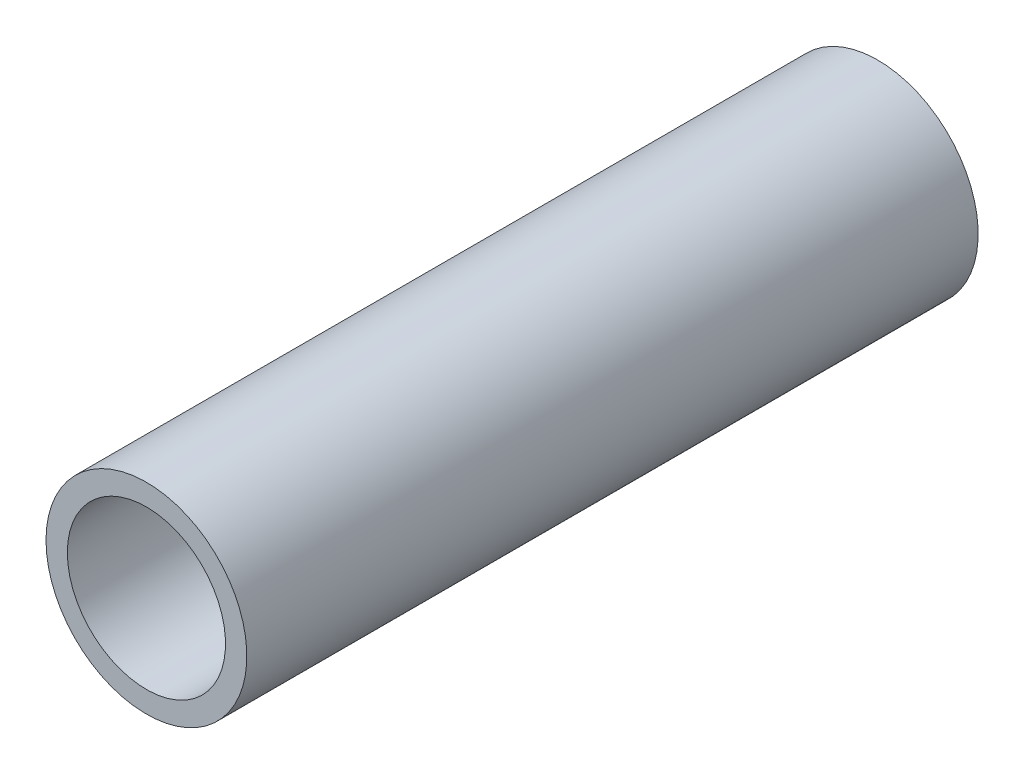
SolidWorks part; units mm, degrees
ref_plane "Front Plane" through (0, 0, 0) normal (0, 0, 1) x (1, 0, 0)
ref_plane "Top Plane" through (0, 0, 0) normal (0, 1, 0) x (1, 0, 0)
ref_plane "Right Plane" through (0, 0, 0) normal (1, 0, 0) x (0, 0, -1)
sketch "Sketch1" plane through (0, 0, 0) normal (0, 0, 1) x (1, 0, 0)
  circle A0 centre (0, 0) radius 4
  circle A1 centre (0, 0) radius 3.15
  dimension "D1" = 8
  dimension "D2" = 6.3
extrude "Boss-Extrude1" add sketch "Sketch1" along normal blind 29.13
